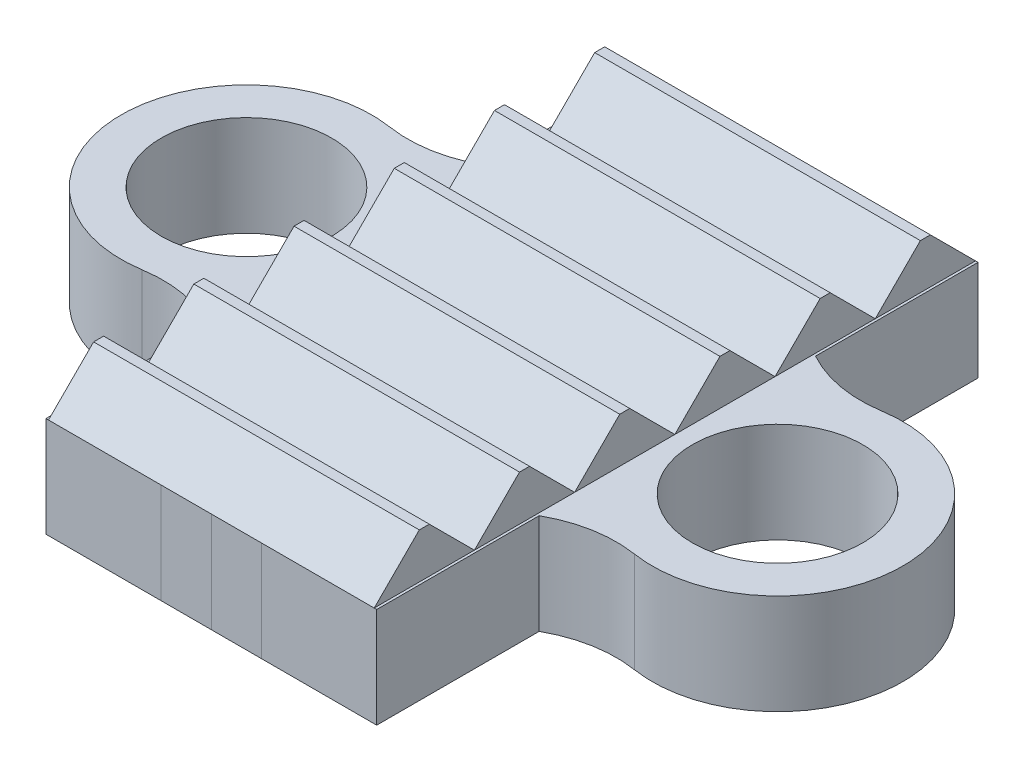
SolidWorks part; units mm, degrees
note: The reader was unsure of these and kept them because the rebuilt part matched: shared geometry of "Sketch1<3>", "Sketch1<4>".
ref_plane "Alzado" through (0, 0, 0) normal (0, 0, 1) x (1, 0, 0)
ref_plane "Planta" through (0, 0, 0) normal (0, 1, 0) x (1, 0, 0)
ref_plane "Vista lateral" through (0, 0, 0) normal (1, 0, 0) x (0, 0, -1)
sketch "Croquis1" plane through (0, 0, 0) normal (0, 1, 0) x (1, 0, 0)
  line L0 (0, -16.4018) -> (0, 78.9163) construction
  line L1 (-63.9099, 0) -> (63.9099, 0) construction
  line L2 (-3.3, 6) -> (3.3, 6)
  line L3 (3.3, 6) -> (3.3, 2.7581)
  line L4 (-3.3, -6) -> (3.3, -6)
  line L5 (3.3, -6) -> (3.3, -2.7581)
  line L6 (-3.3, -6) -> (-3.3, -2.7581)
  line L7 (-3.3, 6) -> (-3.3, 2.7581)
  line L8 (3.3, -2.7581) -> (3.3, 2.7581)
  line L9 (-3.3, -2.7581) -> (-3.3, 2.7581)
  circle A0 centre (5.3, 0) radius 1.7
  arc A1 (4.911, -2.4695) -> (4.911, 2.4695) centre (5.3, 0) ccw
  arc A2 (3.3, 2.7581) -> (4.911, 2.4695) centre (4.5219, 4.9391) ccw
  arc A3 (3.3, -2.7581) -> (4.911, -2.4695) centre (4.5219, -4.9391) cw
  arc A4 (-3.3, -2.7581) -> (-4.911, -2.4695) centre (-4.5219, -4.9391) ccw
  arc A5 (-3.3, 2.7581) -> (-4.911, 2.4695) centre (-4.5219, 4.9391) cw
  arc A6 (-4.911, -2.4695) -> (-4.911, 2.4695) centre (-5.3, 0) cw
  circle A7 centre (-5.3, 0) radius 1.7
  point P6 (7.8, 0)
  point P10 (8, 0)
  point P19 (0, 0)
  point P28 (0, -6)
  point P29 (-8, 0)
  point P30 (0, 6)
  dimension "D1" = 7.8
  dimension "D5" = 5
  dimension "D6" = 5
  dimension "D4" = 6
extrude "Saliente-Extruir1" add sketch "Croquis1" along normal blind 2 contours L9 L6 L4 L5 L8 L3 L2 L7 | L8 A3 A1 A2 A0 | A6 A4 L9 A5 A7
ref_plane "Plano1" through (3.25, 0, 0) normal (1, 0, 0) x (0, 0, -1)
sketch "Croquis4" plane through (3.25, 0, 0) normal (1, 0, 0) x (0, 0, -1)
  line L0 (-6, 2) -> (-4, 2)
  line L1 (-6, 2) -> (-5.1, 2.9)
  line L2 (-5, 3) -> (-5, 2) construction
  line L3 (-4, 2) -> (-4.9, 2.9)
  line L4 (-5.1, 2.9) -> (-4.9, 2.9)
  dimension "D1" = 1
  dimension "D2" = 1
  dimension "D3" = 0.9
extrude "Saliente-Extruir2" add sketch "Croquis4" against normal blind 6.5
pattern_linear "MatrizL1" count 6 spacing 2 along (0, 0, -1) of "Saliente-Extruir2"
sketch "Sketch1" plane through (0, 0, 6) normal (0, 0, 1) x (1, 0, 0)
  line L0 (0, 2) -> (0, 0)
  line L1 (-3.25, 2) -> (3.25, 2) construction
  line L4 (-1, 2) -> (1, 2)
  line L5 (-1, 2) -> (-1, 0)
  line L6 (-1, 0) -> (1, 0)
  line L7 (1, 2) -> (1, 0)
  dimension "D1" = 1
  dimension "D2" = 1
extrude "Cut-Extrude1" cut sketch "Sketch1" against normal blind 0.1
extrude "Boss-Extrude1" add sketch "Sketch1<3>" against normal blind 0.1 separate body
sketch "Sketch1<3>" plane through (0, 0, 6) normal (0, 0, 1) x (1, 0, 0) same geometry as "Sketch1"
extrude "Boss-Extrude2" add sketch "Sketch1<4>" against normal blind 0.1 separate body
sketch "Sketch1<4>" plane through (0, 0, 6) normal (0, 0, 1) x (1, 0, 0) same geometry as "Sketch1"
